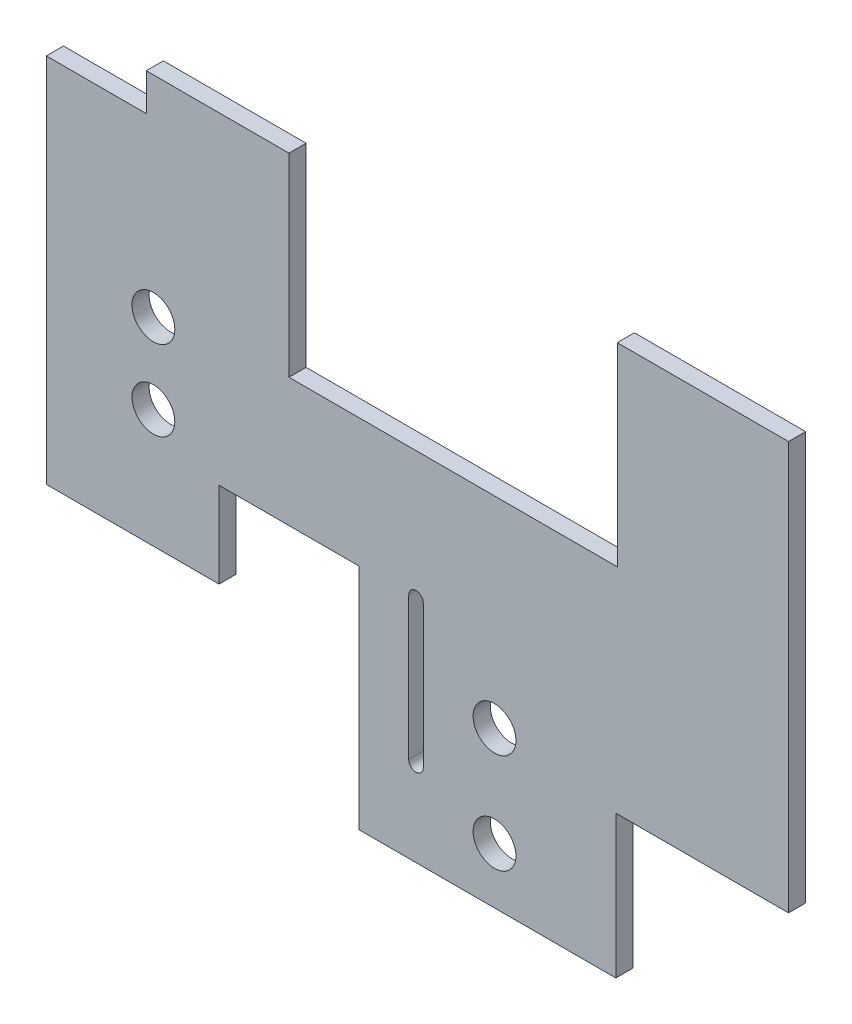
SolidWorks part; units mm, degrees
material "MDF"
ref_plane "Plano frontal" through (0, 0, 0) normal (0, 0, 1) x (1, 0, 0)
ref_plane "Plano superior" through (0, 0, 0) normal (0, 1, 0) x (1, 0, 0)
ref_plane "Plano direito" through (0, 0, 0) normal (1, 0, 0) x (0, 0, -1)
sketch "Esboço1" plane through (0, 0, 0) normal (0, 0, 1) x (1, 0, 0)
  line L0 (-45, 96.5) -> (-45, 28.5)
  line L1 (-130, -96.5) -> (130, -96.5)
  line L2 (-130, -96.5) -> (-130, 96.5)
  line L3 (-130, 96.5) -> (130, 96.5)
  line L4 (130, -96.5) -> (130, 96.5)
  line L5 (-130, -96.5) -> (130, 96.5) construction
  line L6 (-130, 96.5) -> (130, -96.5) construction
  line L7 (-45, 28.5) -> (70, 28.5)
  line L8 (-69.5, -16.5) -> (-20.5, -16.5)
  line L9 (-20.5, -16.5) -> (-20.5, -96.5)
  line L10 (0, 0) -> (0, 96.5) construction
  line L11 (69.5, -146.5) -> (69.5, -46.5)
  line L12 (69.5, -46.5) -> (130, -46.5)
  line L13 (70, 96.5) -> (70, 28.5)
  line L14 (-130, 83.5) -> (-95, 83.5)
  line L15 (-95, 83.5) -> (-95, 96.5)
  line L16 (-69.5, -16.5) -> (-69.5, -46.5)
  line L17 (-69.5, -46.5) -> (-130, -46.5)
  line L18 (-0.5, -66.5) -> (-0.5, -16.5) construction
  line L19 (-3.05, -66.5) -> (-3.05, -16.5)
  line L20 (2.05, -66.5) -> (2.05, -16.5)
  line L21 (-20.5, -41.5) -> (19.5, -41.5) construction
  line L22 (27, -42) -> (27, -77) construction
  arc A0 (-3.05, -66.5) -> (2.05, -66.5) centre (-0.5, -66.5) ccw
  arc A1 (2.05, -16.5) -> (-3.05, -16.5) centre (-0.5, -16.5) ccw
  circle A2 centre (27, -77) radius 7.5
  circle A3 centre (27, -42) radius 7.5
  circle A4 centre (-92.5, -5) radius 7.5
  circle A5 centre (-92.5, 23) radius 7.5
  point P0 (0, 0)
  point P25 (-0.5, -41.5)
  point P36 (19.5, -42)
  point P37 (27, -59.5)
  point P42 (-92.5, 15.5)
  point P43 (-92.5, 2.5)
  point P44 (-92.5, 15.5)
  point P45 (-100, 23)
  dimension "D13" = 2.55
  dimension "D17" = 15
  dimension "D20" = 15
  dimension "D21" = 13
  dimension "D23" = 55
  dimension "D1" = 260
  dimension "D2" = 50
  dimension "D3" = 125
  dimension "D4" = 85
  dimension "D5" = 193
  dimension "D6" = 100
  dimension "D7" = 60.5
  dimension "D8" = 90
  dimension "D9" = 80
  dimension "D10" = 60
  dimension "D11" = 35
  dimension "D12" = 180
  dimension "D14" = 50
  dimension "D15" = 20
  dimension "D16" = 30
  dimension "D18" = 35
  dimension "D19" = 37
  dimension "D22" = 13
extrude "Ressalto-extrusão1" add sketch "Esboço1" along normal blind 6 contours L3 L7 L0 L2 L1 L11 L12 L4 region at (4.9471, 4.9635, 0)
